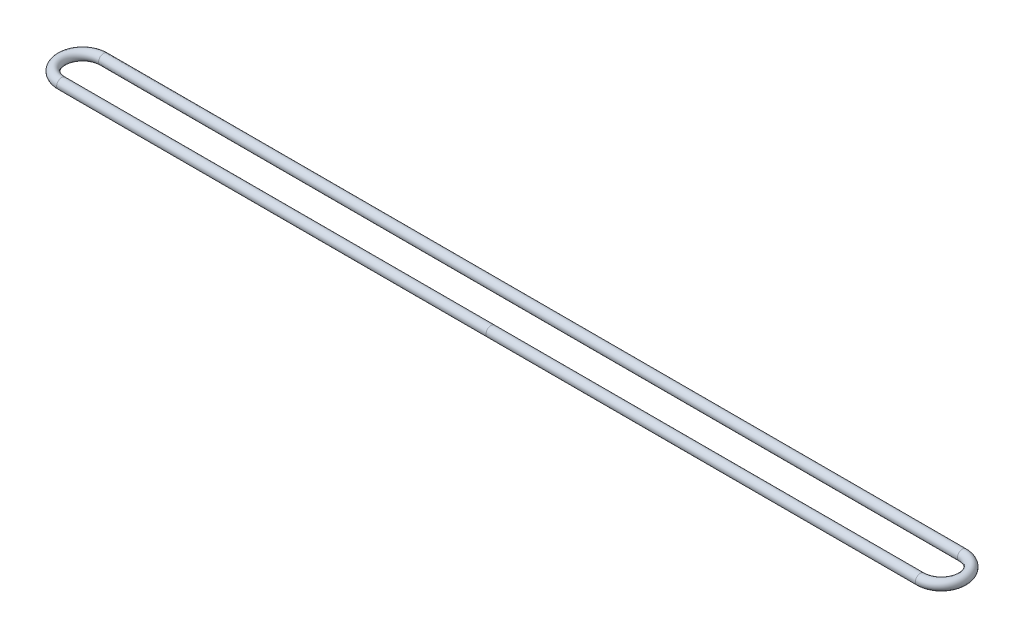
SolidWorks part; units mm, degrees
ref_plane "Front Plane" through (0, 0, 0) normal (0, 0, 1) x (1, 0, 0)
ref_plane "Top Plane" through (0, 0, 0) normal (0, 1, 0) x (1, 0, 0)
ref_plane "Right Plane" through (0, 0, 0) normal (1, 0, 0) x (0, 0, -1)
sketch "Sketch1" plane through (0, 0, 0) normal (0, 1, 0) x (1, 0, 0)
  line L0 (-142.875, 0) -> (142.875, 0) construction
  line L1 (-142.875, 6.985) -> (142.875, 6.985)
  line L2 (-142.875, -6.985) -> (142.875, -6.985)
  arc A0 (-142.875, 6.985) -> (-142.875, -6.985) centre (-142.875, 0) ccw
  arc A1 (142.875, -6.985) -> (142.875, 6.985) centre (142.875, 0) ccw
  point P3 (0, 0)
  dimension "D1" = 285.75
  dimension "D2" = 13.97
sketch "Sketch2" plane through (0, 0, 0) normal (1, 0, 0) x (0, 0, -1)
  line L0 (6.985, 0) -> (-6.985, 0) construction
  circle A0 centre (-6.985, 0) radius 1.651
  dimension "D1" = 3.302
sweep "Sweep1" add profiles "Sketch2" path "Sketch1"
ref_axis "Axis1" through (142.875, 0, 0) along (0, 1, 0)
ref_axis "Axis2" through (-142.875, 0, 0) along (0, 1, 0)
